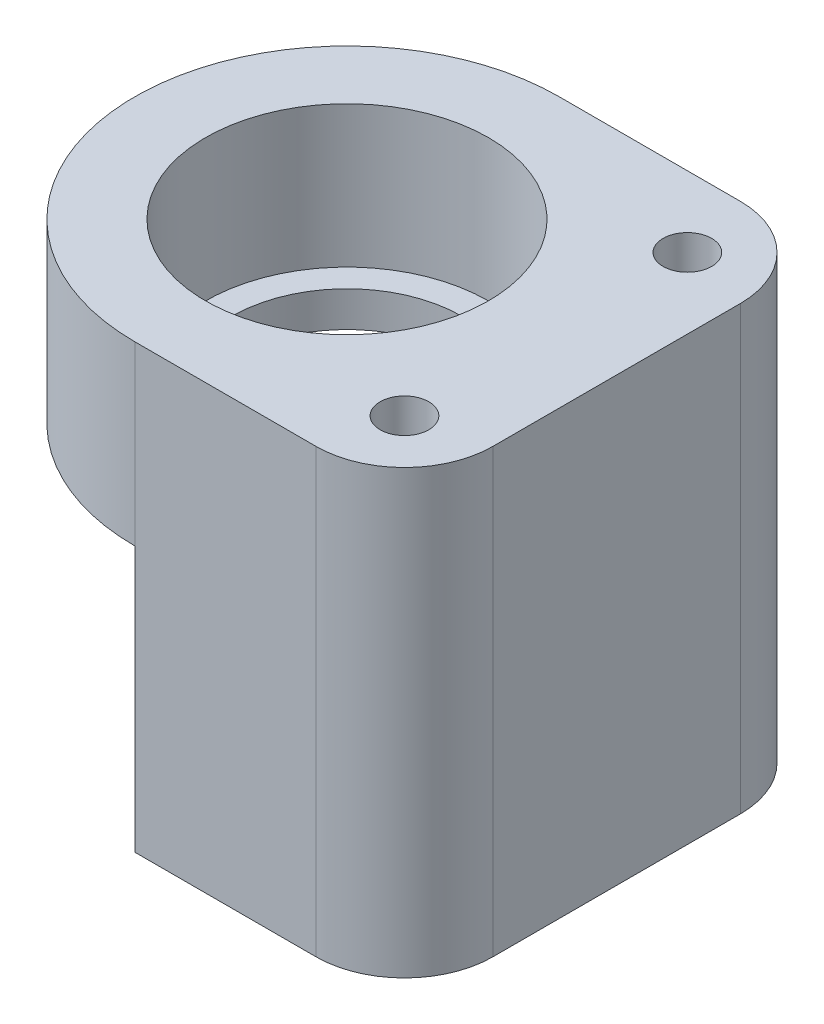
SolidWorks part; units mm, degrees
note: '?' marks a value the reader was unsure of.
ref_plane "Front Plane" through (0, 0, 0) normal (0, 0, 1) x (1, 0, 0)
ref_plane "Top Plane" through (0, 0, 0) normal (0, 1, 0) x (1, 0, 0)
ref_plane "Right Plane" through (0, 0, 0) normal (1, 0, 0) x (0, 0, -1)
ref_axis "X" through (88.99, 0, 0) along (-1, 0, 0)?
ref_axis "Y" through (0, 55, 0) along (0, -1, 0)?
ref_axis "Z" through (0, 0, -88.99) along (0, 0, 1)?
sketch "Sketch1" plane through (0, 0, 0) normal (0, 0, 1) x (1, 0, 0)
  line L0 (0, 0) -> (0, 52.8087) construction
  line L4 (-24, 0) -> (-24, 50)
  line L9 (-20, 30) -> (-16, 30)
  line L10 (-16, 34) -> (-16, 50)
  line L13 (-16, 50) -> (-24, 50)
  line L14 (-24, 0) -> (-20, 0)
  line L16 (-20, 0) -> (-20, 30)
  line L17 (-16, 30) -> (-13, 30)
  line L18 (-13, 30) -> (-13, 34)
  line L19 (-13, 34) -> (-16, 34)
  point P3 (0, 0)
  dimension "D2" = 32
  dimension "D3" = 30
  dimension "D4" = 48
  dimension "D5" = 40
  dimension "D6" = 4
  dimension "D7" = 26
  dimension "D10" = 50
revolve "Revolve1" add sketch "Sketch1" angle 360 about L0
sketch "Sketch5" plane through (0, 0, 0) normal (0, 1, 0) x (1, 0, 0)
  line L5 (-38.7914, 24) -> (0, 24)
  line L6 (-38.7914, 24) -> (-38.7914, -24)
  line L7 (-38.7914, -24) -> (0, -24)
  line L8 (0, 24) -> (0, -24)
  circle A3 centre (0, 0) radius 24 construction
extrude "Cut-Extrude1" cut sketch "Sketch5" along normal blind 30
sketch "Sketch6" plane through (0, 50, 0) normal (0, 1, 0) x (1, 0, 0)
  line L3 (0, -24) -> (20.5, -24)
  line L4 (30.5, -14) -> (30.5, 14)
  line L5 (20.5, 24) -> (0, 24)
  arc A3 (0, -24) -> (0, 24) centre (0, 0) ccw
  arc A4 (20.5, -24) -> (30.5, -14) centre (20.5, -14) ccw
  arc A5 (30.5, 14) -> (20.5, 24) centre (20.5, 14) ccw
  dimension "D2" = 10
  dimension "D3" = 10
  dimension "D4" = 24
  dimension "D1" = 30.5
extrude "Boss-Extrude1" add sketch "Sketch6" against normal up to surface (50 mm away) up to face at (11, 0, 0)
hole_wizard "Ø3.0mm Dowel Hole1" [suppressed] positions "Sketch7" profile "Sketch8" hole size "Ø3.0" standard "DIN"
sketch "Sketch7" plane through (0, 0, 0) normal (0, -1, 0) x (-1, 0, 0)
  line L0 (-20.5, -24) -> (0, -24) construction
  line L1 (-30.5, 14) -> (-30.5, -14) construction
  line L2 (0, 24) -> (-20.5, 24) construction
  point P0 (-24.5, -9)
  point P2 (-24.5, 9)
  dimension "D1" = 15
  dimension "D3" = 6
  dimension "D4" = 15
sketch "Sketch8" plane through (24.5, 0, 9) normal (1, 0, 0) x (0, 0, -1)
  line L0 (0, 0) -> (0, 6.9013)
  line L1 (0, 6.9013) -> (1.5, 6)
  line L2 (1.5, 6) -> (1.5, 0)
  line L5 (1.5, 0) -> (0, 0)
  line L10 (0, 6.9013) -> (-1.5, 6) construction
  line L11 (0, -6.35) -> (0, 107.95) construction
  dimension "Hole Dia." = 3
  dimension "Hole Depth" = 6
  dimension "Drill Angle" = 118
hole_wizard "M5 Clearance Hole1" positions "Sketch11" profile "Sketch12" hole size "M5" standard "DIN" end condition up to next
sketch "Sketch11" plane through (0, 0, 0) normal (0, -1, 0) x (-1, 0, 0)
  line L0 (-20.5, -24) -> (0, -24) construction
  line L1 (-30.5, 14) -> (-30.5, -14) construction
  line L2 (0, 24) -> (-20.5, 24) construction
  point P0 (-22.5, -16)
  point P2 (-22.5, 16)
  dimension "D1" = 8
  dimension "D2" = 8
  dimension "D3" = 8
sketch "Sketch12" plane through (22.5, 0, 16) normal (1, 0, 0) x (0, 0, -1)
  line L0 (0, 0) -> (0, 50)
  line L1 (0, 50) -> (2.75, 50)
  line L2 (2.75, 50) -> (2.75, 0)
  line L5 (2.75, 0) -> (0, 0)
  line L11 (0, -6.35) -> (0, 107.95) construction
  dimension "Thru Hole Dia." = 5.5
  dimension "Thru Hole Depth" = 50
